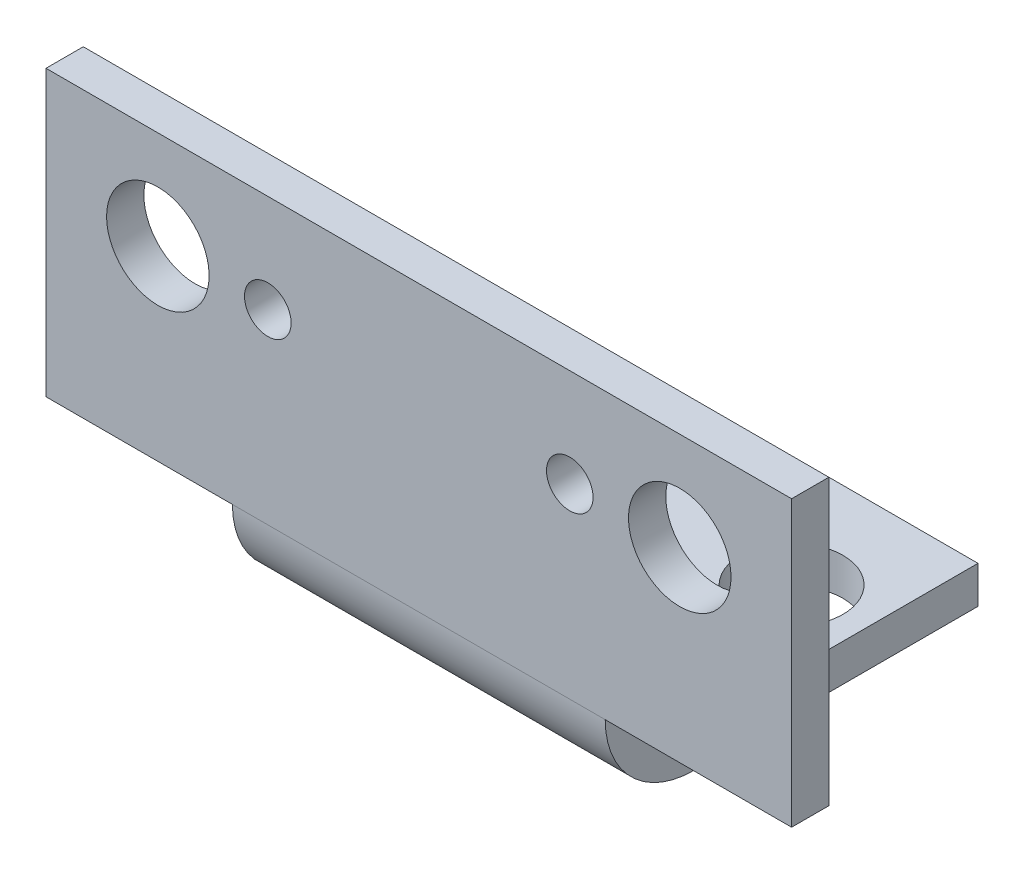
SolidWorks part; units mm, degrees
note: The reader was unsure of these and kept them because the rebuilt part matched: flange length of "边线-法兰1".
ref_plane "前视基准面" through (0, 0, 0) normal (0, 0, 1) x (1, 0, 0)
ref_plane "上视基准面" through (0, 0, 0) normal (0, 1, 0) x (1, 0, 0)
ref_plane "右视基准面" through (0, 0, 0) normal (1, 0, 0) x (0, 0, -1)
sketch "草图1" plane through (0, 0, 0) normal (0, 1, 0) x (1, 0, 0)
  line L1 (-10, -10) -> (10, -10)
  line L2 (-10, -10) -> (-10, 10)
  line L3 (-10, 10) -> (10, 10)
  line L4 (10, -10) -> (10, 10)
  line L5 (-10, -10) -> (10, 10) construction
  line L6 (-10, 10) -> (10, -10) construction
  point P0 (0, 0)
  dimension "D1" = 20
  dimension "D2" = 20
base flange "基体-法兰1" sketch "草图1" thickness 2 reverse thickness direction no parameters "D1"=2.7366
edge flange "边线-法兰1" sketch "草图8" flange angle 90 flange length 20 flange position material inside bend radius 2.7366 thickness 2 relief rectangular parameters "D6"=10
sketch "草图8" plane through (0, 0, 10) normal (0, 0, -1) x (-1, 0, 0)
  line L1 (10, 0) -> (-10, 0) construction
  line L2 (-20, 0) -> (-20, 18)
  line L3 (-20, 18) -> (20, 18)
  line L4 (20, 18) -> (20, 0)
  line L5 (20, 0) -> (-20, 0)
  dimension "D1" = 18
  dimension "D2" = 40
  dimension "D3" = 20
bend "边线折弯1" bend radius 2.7366 bend angle 90 parameters "D5"=1
sketch "草图9" plane through (0, 0, 10) normal (0, 0, 1) x (1, 0, 0)
  line L0 (14, 12.7366) -> (-14, 12.7366) construction
  line L1 (0, 2.7366) -> (0, 18) construction
  line L2 (-10, 2.7366) -> (10, 2.7366) construction
  line L3 (-20, 18) -> (20, 18) construction
  line L4 (-10, 2.7366) -> (10, 2.7366) construction
  circle A0 centre (14, 12.7366) radius 2.75
  circle A1 centre (8.1, 12.7366) radius 1.25
  circle A2 centre (-8.1, 12.7366) radius 1.25
  circle A3 centre (-14, 12.7366) radius 2.75
  point P1 (13.8041, 10.124)
  point P16 (-13.6415, 10.4652)
  dimension "D1" = 5.5
  dimension "D2" = 2.5
  dimension "D3" = 16.2
  dimension "D4" = 28
  dimension "D5" = 10
extrude "切除-拉伸1" cut sketch "草图9" against normal blind 10 normal cut yes
sketch "草图10" plane through (0, -2, 0) normal (0, -1, 0) x (1, 0, 0)
  line L0 (6, -4) -> (-6, -4) construction
  line L1 (10, -10) -> (-10, -10) construction
  circle A0 centre (6, -4) radius 2.75
  circle A1 centre (-6, -4) radius 2.75
  point P4 (0, 0)
  dimension "D1" = 12
  dimension "D3" = 5.5
  dimension "D2" = 6
  dimension "D4" = 6
extrude "切除-拉伸2" cut sketch "草图10" against normal blind 10 normal cut yes
sketch "折弯-线1" plane through (0, 0, 0) normal (0, 1, 0) x (1, 0, 0)
sketch "边界框1" plane through (0, 0, 0) normal (0, 1, 0) x (1, 0, 0)
sheet metal parameters "钣金6" thickness 2 parameters "D1"=2.7366
flat pattern "平板型式6" [suppressed]
sketch "折弯-线2" plane through (0, 0, 0) normal (0, 1, 0) x (1, 0, 0)
sketch "边界框2" [suppressed] plane through (0, 0, 0) normal (0, 1, 0) x (1, 0, 0)
sheet metal parameters "钣金7" thickness 2 parameters "D1"=2.7366
flat pattern "平板型式6" [suppressed]
sketch "折弯-线2" plane through (0, 0, 0) normal (0, 1, 0) x (1, 0, 0)
sketch "边界框2" [suppressed] plane through (0, 0, 0) normal (0, 1, 0) x (1, 0, 0)
bend of the flat pattern "展开-<边线折弯1>1"
sheet metal parameters "钣金8" thickness 2 parameters "D1"=2.7366
flat pattern "平板型式6" [suppressed]
sketch "折弯-线2" plane through (0, 0, 0) normal (0, 1, 0) x (1, 0, 0)
sketch "边界框2" [suppressed] plane through (0, 0, 0) normal (0, 1, 0) x (1, 0, 0)
bend of the flat pattern "展开-<边线折弯1>1"
sheet metal parameters "钣金9" thickness 2 parameters "D1"=2.7366
flat pattern "平板型式6" [suppressed]
sketch "折弯-线2" plane through (0, 0, 0) normal (0, 1, 0) x (1, 0, 0)
sketch "边界框2" [suppressed] plane through (0, 0, 0) normal (0, 1, 0) x (1, 0, 0)
bend of the flat pattern "展开-<边线折弯1>1"
